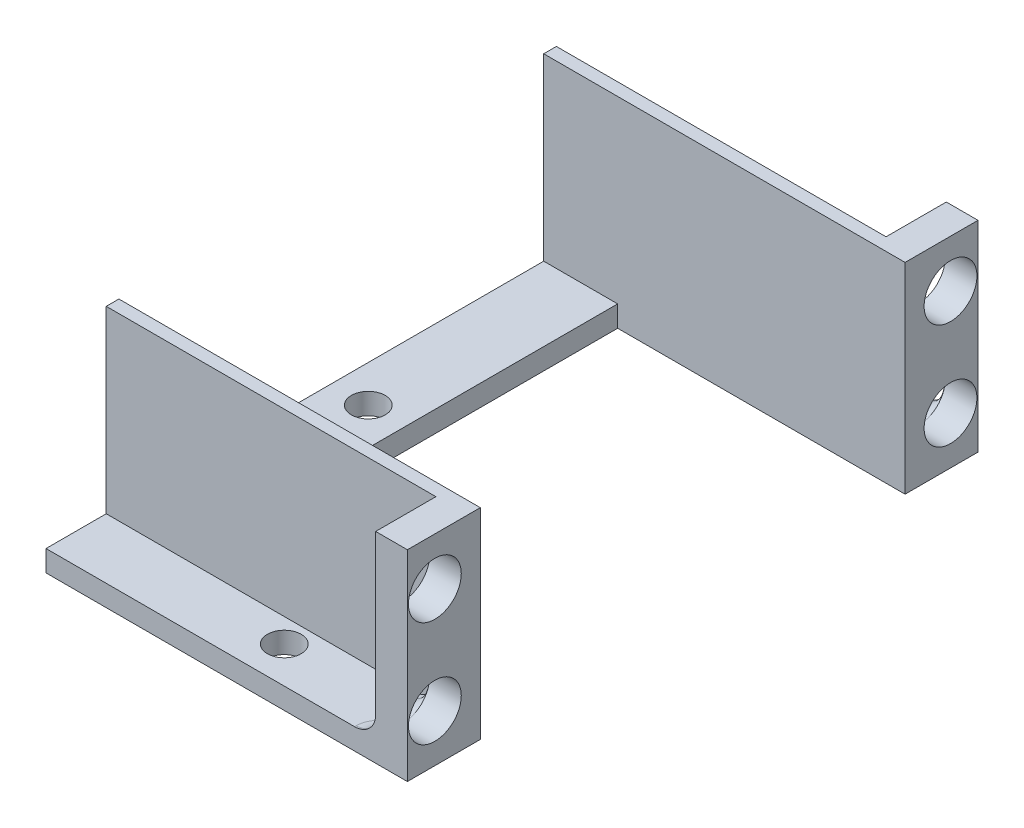
SolidWorks part; units mm, degrees
ref_plane "Plan de face" through (0, 0, 0) normal (0, 0, 1) x (1, 0, 0)
ref_plane "Plan de dessus" through (0, 0, 0) normal (0, 1, 0) x (1, 0, 0)
ref_plane "Plan de droite" through (0, 0, 0) normal (1, 0, 0) x (0, 0, -1)
sketch "Esquisse1" plane through (0, 0, 0) normal (0, 1, 0) x (1, 0, 0)
  line L0 (0, 0) -> (31.2, 0)
  line L2 (31.2, 6.9) -> (7, 6.9)
  line L3 (7, 6.9) -> (7, 47.1)
  line L4 (7, 47.1) -> (31.2, 47.1)
  line L5 (31.2, 47.1) -> (31.2, 54)
  line L6 (31.2, 54) -> (0, 54)
  line L7 (0, 54) -> (0, 0)
  line L8 (32, 54) -> (32, 47.1) construction
  line L10 (31.2, 6.9) -> (31.2, 0) construction
  line L11 (32, 54) -> (32, 47.1)
  line L12 (31.2, 6.9) -> (31.2, 0)
  dimension "D1" = 6.9
  dimension "D2" = 40.2
  dimension "D3" = 31.2
  dimension "D4" = 7
extrude "Boss.-Extru.1" add sketch "Esquisse1" along normal blind 2 contours L12 L2 L3 L4 L11 L6 L7 L0 region at (0.6237, 0, -27)
sketch "Esquisse2" plane through (0, 0, 0) normal (0, 1, 0) x (1, 0, 0)
  line L0 (31.2, 54) -> (34.2, 54)
  line L1 (34.2, 54) -> (34.2, 47.1)
  line L2 (31.2, 54) -> (31.2, 47.1)
  line L3 (31.2, 47.1) -> (34.2, 47.1)
  line L4 (31.2, 6.9) -> (31.2, 0)
  line L5 (31.2, 0) -> (34.2, 0)
  line L6 (34.2, 0) -> (34.2, 6.9)
  line L7 (34.2, 6.9) -> (31.2, 6.9)
  dimension "D1" = 3
extrude "Boss.-Extru.2" add sketch "Esquisse2" along normal blind 19
sketch "Esquisse3" plane through (34.2, 0, 0) normal (1, 0, 0) x (0, 0, -1)
  line L0 (0, 9.5) -> (6.9, 9.5) construction
  line L1 (0, 19) -> (0, 0) construction
  line L2 (6.9, 19) -> (6.9, 0) construction
  line L4 (27, 0) -> (27, 2) construction
  line L5 (6.9, 0) -> (47.1, 0) construction
  line L6 (6.9, 2) -> (47.1, 2) construction
  circle A0 centre (2.6, 4.5) radius 2.5
  circle A1 centre (2.6, 14.5) radius 2.5
  circle A2 centre (51.4, 4.5) radius 2.5
  circle A3 centre (51.4, 14.5) radius 2.5
  dimension "D1" = 5
  dimension "D2" = 4.5
  dimension "D3" = 2.6
extrude "Enlèv. mat.-Extru.1" cut sketch "Esquisse3" against normal up to next
sketch "Esquisse4" plane through (0, 0, 0) normal (0, 1, 0) x (1, 0, 0)
  line L1 (0, 27) -> (7, 27) construction
  line L2 (0, 54) -> (0, 0) construction
  line L3 (7, 6.9) -> (7, 47.1) construction
  line L4 (19.1, 6.9) -> (19.1, 0) construction
  line L5 (31.2, 6.9) -> (7, 6.9) construction
  line L6 (0, 0) -> (31.2, 0) construction
  circle A0 centre (19.1, 3.45) radius 1.6
  circle A1 centre (3.5, 27) radius 1.6
  circle A2 centre (19.1, 50.3269) radius 1.6
  dimension "D1" = 3.2
extrude "Enlèv. mat.-Extru.2" cut sketch "Esquisse4" along normal up to next
fillet "Congé1" radius 2 4 edges at (31.2, 2, -1.3) (31.2, 2, -52.7) (31.2, 2, -4.75) (31.2, 2, -49.25)
ref_plane "Plan1" through (0, 0, -27) normal (0, 0, -1) x (-1, 0, 0)
sketch "Esquisse6" plane through (0, 0, -47.1) normal (0, 0, 1) x (1, 0, 0)
  line L0 (34.2, 19) -> (34.2, 0)
  line L1 (34.2, 0) -> (0, 0)
  line L2 (0, 0) -> (0, 2)
  line L3 (0, 2) -> (0, 19)
  line L4 (0, 19) -> (34.2, 19)
extrude "Boss.-Extru.3" add sketch "Esquisse6" against normal blind 1.2
mirror "Symétrie1" about plane through (0, 0, -27) normal (0, 0, -1) of "Boss.-Extru.3"
